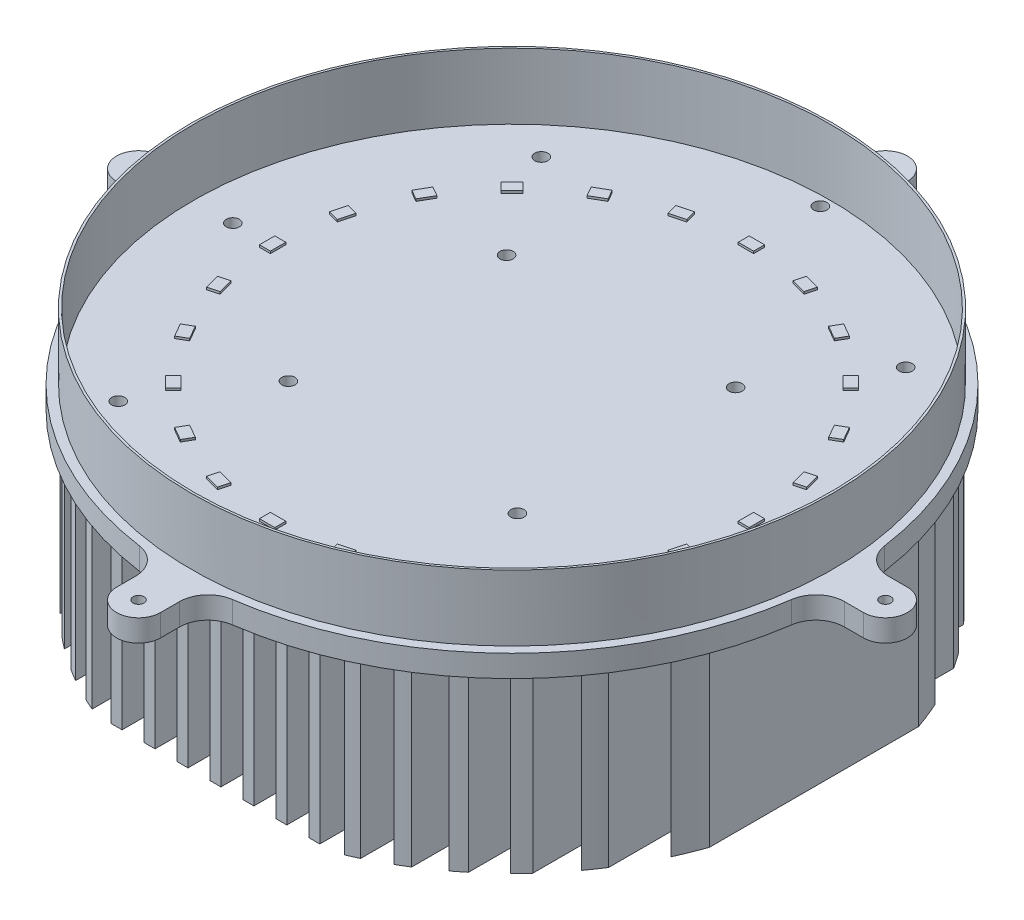
SolidWorks part; units mm, degrees
ref_plane "Front Plane" through (0, 0, 0) normal (0, 0, 1) x (1, 0, 0)
ref_plane "Top Plane" through (0, 0, 0) normal (0, 1, 0) x (1, 0, 0)
ref_plane "Right Plane" through (0, 0, 0) normal (1, 0, 0) x (0, 0, -1)
sketch "Sketch2" plane through (0, 0, 0) normal (0, 1, 0) x (1, 0, 0)
  line L0 (0, 0) -> (0, -224.3017) construction
  line L1 (0, 0) -> (0, 200) construction
  line L2 (0, 0) -> (207.2583, 0) construction
  line L3 (0, 0) -> (-200, 0) construction
  circle A0 centre (0, 0) radius 146
  circle A1 centre (0, 0) radius 145
  point P36 (0, 0)
  dimension "D1" = 290
  dimension "D2" = 292
extrude "Boss-Extrude2" add sketch "Sketch2" along normal blind 30 contours A1 | A0
sketch "Sketch3" plane through (0, 0, 0) normal (0, 1, 0) x (1, 0, 0)
  line L0 (0, 0) -> (211.9111, 0) construction
  line L1 (0, 0) -> (-205.2426, 0) construction
  line L2 (0, 0) -> (0, 170) construction
  line L3 (0, 0) -> (0, -200) construction
  line L4 (161.3691, 10) -> (170, 10)
  line L5 (161.3691, -10) -> (170, -10)
  line L6 (-10, 161.3691) -> (-10, 170)
  line L7 (10, 161.3691) -> (10, 170)
  line L8 (10, -161.3691) -> (10, -170)
  line L9 (-10, -161.3691) -> (-10, -170)
  line L10 (-161.3691, -10) -> (-170, -10)
  line L11 (-161.3691, 10) -> (-170, 10)
  arc A0 (-21.1656, 148.4992) -> (-148.4992, 21.1656) centre (0, 0) ccw
  circle A1 centre (0, 170) radius 2.5
  arc A2 (-10, 170) -> (10, 170) centre (0, 170) cw
  arc A3 (10, 161.3691) -> (21.1656, 148.4992) centre (23, 161.3691) ccw
  arc A4 (-10, 161.3691) -> (-21.1656, 148.4992) centre (-23, 161.3691) cw
  arc A5 (170, 10) -> (170, -10) centre (170, 0) cw
  arc A6 (161.3691, 10) -> (148.4992, 21.1656) centre (161.3691, 23) cw
  circle A7 centre (170, 0) radius 2.5
  arc A8 (161.3691, -10) -> (148.4992, -21.1656) centre (161.3691, -23) ccw
  arc A9 (10, -170) -> (-10, -170) centre (0, -170) cw
  arc A10 (10, -161.3691) -> (21.1656, -148.4992) centre (23, -161.3691) cw
  circle A11 centre (0, -170) radius 2.5
  arc A12 (-10, -161.3691) -> (-21.1656, -148.4992) centre (-23, -161.3691) ccw
  arc A13 (-170, -10) -> (-170, 10) centre (-170, 0) cw
  arc A14 (-161.3691, -10) -> (-148.4992, -21.1656) centre (-161.3691, -23) cw
  circle A15 centre (-170, 0) radius 2.5
  arc A16 (-161.3691, 10) -> (-148.4992, 21.1656) centre (-161.3691, 23) ccw
  arc A17 (-148.4992, -21.1656) -> (-21.1656, -148.4992) centre (0, 0) ccw
  arc A18 (148.4992, 21.1656) -> (21.1656, 148.4992) centre (0, 0) ccw
  arc A19 (21.1656, -148.4992) -> (148.4992, -21.1656) centre (0, 0) ccw
  point P53 (0, 0)
  dimension "D1" = 300
  dimension "D4" = 5
  dimension "D2" = 4
extrude "Boss-Extrude4" add sketch "Sketch3" against normal blind 10
sketch "Sketch4" plane through (0, -10, 0) normal (0, -1, 0) x (1, 0, 0)
  line L0 (0, 0) -> (0, -192.7937) construction
  line L1 (0, 0) -> (0, 216.5128) construction
  line L2 (0, 0) -> (-235.9747, 0) construction
  line L3 (0, 0) -> (242.3846, 0) construction
  line L4 (2.5, -135) -> (-2.5, -135)
  line L5 (2.5, 135) -> (-2.5, 135)
  line L6 (-2.5, -135) -> (-2.5, 135)
  line L7 (2.5, -135) -> (2.5, 135)
  line L8 (12.5, -135) -> (12.5, 135)
  line L9 (17.5, -135) -> (12.5, -135)
  line L10 (17.5, -135) -> (17.5, 135)
  line L11 (17.5, 135) -> (12.5, 135)
  line L12 (27.5, -135) -> (27.5, 135)
  line L13 (32.5, -135) -> (27.5, -135)
  line L14 (32.5, -135) -> (32.5, 135)
  line L15 (32.5, 135) -> (27.5, 135)
  line L16 (42.5, -135) -> (42.5, 135)
  line L17 (47.5, -135) -> (42.5, -135)
  line L18 (47.5, -135) -> (47.5, 135)
  line L19 (47.5, 135) -> (42.5, 135)
  line L20 (57.5, -133.6563) -> (57.5, 133.6563)
  line L22 (62.5, -131.3925) -> (62.5, 131.3925)
  line L24 (72.5, -126.1507) -> (72.5, 126.1507)
  line L26 (77.5, -123.1422) -> (77.5, 123.1422)
  line L28 (87.5, -116.2497) -> (87.5, 116.2497)
  line L30 (92.5, -112.3121) -> (92.5, 112.3121)
  line L32 (102.5, -103.2666) -> (102.5, 103.2666)
  line L34 (107.5, -98.051) -> (107.5, 98.051)
  line L36 (117.5, -85.8138) -> (117.5, 85.8138)
  line L38 (122.5, -78.5111) -> (122.5, 78.5111)
  line L40 (132.5, -60.1166) -> (132.5, 60.1166)
  line L42 (137.5, -47.5815) -> (137.5, 47.5815)
  line L44 (-12.5, -135) -> (-17.5, -135)
  line L45 (-12.5, -135) -> (-12.5, 135)
  line L46 (-17.5, -135) -> (-17.5, 135)
  line L47 (-12.5, 135) -> (-17.5, 135)
  line L48 (-27.5, -135) -> (-32.5, -135)
  line L49 (-27.5, -135) -> (-27.5, 135)
  line L50 (-32.5, -135) -> (-32.5, 135)
  line L51 (-27.5, 135) -> (-32.5, 135)
  line L52 (-42.5, -135) -> (-47.5, -135)
  line L53 (-42.5, -135) -> (-42.5, 135)
  line L54 (-47.5, -135) -> (-47.5, 135)
  line L55 (-42.5, 135) -> (-47.5, 135)
  line L57 (-57.5, -133.6563) -> (-57.5, 133.6563)
  line L58 (-62.5, -131.3925) -> (-62.5, 131.3925)
  line L61 (-72.5, -126.1507) -> (-72.5, 126.1507)
  line L62 (-77.5, -123.1422) -> (-77.5, 123.1422)
  line L65 (-87.5, -116.2497) -> (-87.5, 116.2497)
  line L66 (-92.5, -112.3121) -> (-92.5, 112.3121)
  line L69 (-102.5, -103.2666) -> (-102.5, 103.2666)
  line L70 (-107.5, -98.051) -> (-107.5, 98.051)
  line L73 (-117.5, -85.8138) -> (-117.5, 85.8138)
  line L74 (-122.5, -78.5111) -> (-122.5, 78.5111)
  line L77 (-132.5, -60.1166) -> (-132.5, 60.1166)
  line L78 (-137.5, -47.5815) -> (-137.5, 47.5815)
  line L80 (2.5, -135) -> (-12.5, -135) construction
  line L81 (62.5, 135) -> (57.5, 135) [skipped]
  line L82 (77.5, 135) -> (72.5, 135) [skipped]
  line L83 (92.5, 135) -> (87.5, 135) [skipped]
  line L84 (107.5, 135) -> (102.5, 135) [skipped]
  line L85 (137.5, 135) -> (132.5, 135) [skipped]
  line L86 (122.5, 135) -> (117.5, 135) [skipped]
  line L87 (-57.5, 135) -> (-62.5, 135) [skipped]
  line L88 (-72.5, 135) -> (-77.5, 135) [skipped]
  line L89 (-87.5, 135) -> (-92.5, 135) [skipped]
  line L90 (-102.5, 135) -> (-107.5, 135) [skipped]
  line L91 (-117.5, 135) -> (-122.5, 135) [skipped]
  line L92 (-132.5, 135) -> (-137.5, 135) [skipped]
  line L93 (-57.5, -135) -> (-62.5, -135) [skipped]
  line L94 (62.5, -135) -> (57.5, -135) [skipped]
  line L95 (77.5, -135) -> (72.5, -135) [skipped]
  line L96 (137.5, -135) -> (132.5, -135) [skipped]
  line L97 (122.5, -135) -> (117.5, -135) [skipped]
  line L98 (107.5, -135) -> (102.5, -135) [skipped]
  line L99 (92.5, -135) -> (87.5, -135) [skipped]
  line L100 (-132.5, -135) -> (-137.5, -135) [skipped]
  line L101 (-117.5, -135) -> (-122.5, -135) [skipped]
  line L102 (-102.5, -135) -> (-107.5, -135) [skipped]
  line L103 (-87.5, -135) -> (-92.5, -135) [skipped]
  line L104 (-72.5, -135) -> (-77.5, -135) [skipped]
  arc A2 (132.5, -60.1166) -> (137.5, -47.5815) centre (0, 0) ccw
  arc A3 (117.5, -85.8138) -> (122.5, -78.5111) centre (0, 0) ccw
  arc A4 (102.5, -103.2666) -> (107.5, -98.051) centre (0, 0) ccw
  arc A5 (87.5, -116.2497) -> (92.5, -112.3121) centre (0, 0) ccw
  arc A6 (72.5, -126.1507) -> (77.5, -123.1422) centre (0, 0) ccw
  arc A7 (57.5, -133.6563) -> (62.5, -131.3925) centre (0, 0) ccw
  arc A8 (-77.5, -123.1422) -> (-72.5, -126.1507) centre (0, 0) ccw
  arc A9 (-62.5, -131.3925) -> (-57.5, -133.6563) centre (0, 0) ccw
  arc A10 (-92.5, -112.3121) -> (-87.5, -116.2497) centre (0, 0) ccw
  arc A11 (-107.5, -98.051) -> (-102.5, -103.2666) centre (0, 0) ccw
  arc A12 (-122.5, -78.5111) -> (-117.5, -85.8138) centre (0, 0) ccw
  arc A13 (-137.5, -47.5815) -> (-132.5, -60.1166) centre (0, 0) ccw
  arc A14 (137.5, 47.5815) -> (132.5, 60.1166) centre (0, 0) ccw
  arc A15 (122.5, 78.5111) -> (117.5, 85.8138) centre (0, 0) ccw
  arc A16 (107.5, 98.051) -> (102.5, 103.2666) centre (0, 0) ccw
  arc A17 (92.5, 112.3121) -> (87.5, 116.2497) centre (0, 0) ccw
  arc A18 (77.5, 123.1422) -> (72.5, 126.1507) centre (0, 0) ccw
  arc A19 (62.5, 131.3925) -> (57.5, 133.6563) centre (0, 0) ccw
  arc A20 (-57.5, 133.6563) -> (-62.5, 131.3925) centre (0, 0) ccw
  arc A21 (-72.5, 126.1507) -> (-77.5, 123.1422) centre (0, 0) ccw
  arc A22 (-87.5, 116.2497) -> (-92.5, 112.3121) centre (0, 0) ccw
  arc A23 (-102.5, 103.2666) -> (-107.5, 98.051) centre (0, 0) ccw
  arc A24 (-117.5, 85.8138) -> (-122.5, 78.5111) centre (0, 0) ccw
  arc A25 (-132.5, 60.1166) -> (-137.5, 47.5815) centre (0, 0) ccw
  dimension "D5" = 291
  dimension "D1" = 135
  dimension "D2" = 2.5
  dimension "D4" = 15
  dimension "D3" = 10
extrude "Boss-Extrude5" add sketch "Sketch4" along normal blind 80
sketch "Sketch5" plane through (0, 0, 0) normal (0, 1, 0) x (1, 0, 0)
  line L0 (0, 0) -> (233.0388, 0) construction
  line L1 (0, 0) -> (-266.1331, 0) construction
  line L2 (0, 0) -> (0, 192.8201) construction
  line L3 (0, 0) -> (0, -200.634) construction
  line L4 (0, 111.4786) -> (3.5, 111.4786)
  line L5 (0, 111.4786) -> (-3.5, 111.4786)
  line L6 (3.5, 106.4786) -> (3.5, 111.4786)
  line L7 (-3.5, 106.4786) -> (-3.5, 111.4786)
  line L8 (0, 106.4786) -> (3.5, 106.4786)
  line L9 (0, 106.4786) -> (-3.5, 106.4786)
  line L10 (24.1779, 103.7563) -> (25.472, 108.5859)
  line L11 (28.8528, 107.68) -> (25.472, 108.5859)
  line L12 (28.8528, 107.68) -> (32.2335, 106.7742)
  line L13 (30.9394, 101.9445) -> (32.2335, 106.7742)
  line L14 (27.5587, 102.8504) -> (30.9394, 101.9445)
  line L15 (27.5587, 102.8504) -> (24.1779, 103.7563)
  line L16 (50.2082, 93.9631) -> (52.7082, 98.2933)
  line L17 (55.7393, 96.5433) -> (52.7082, 98.2933)
  line L18 (55.7393, 96.5433) -> (58.7704, 94.7933)
  line L19 (56.2704, 90.4631) -> (58.7704, 94.7933)
  line L20 (53.2393, 92.2131) -> (56.2704, 90.4631)
  line L21 (53.2393, 92.2131) -> (50.2082, 93.9631)
  line L22 (72.8168, 77.7666) -> (76.3524, 81.3021)
  line L23 (78.8273, 78.8273) -> (76.3524, 81.3021)
  line L24 (78.8273, 78.8273) -> (81.3021, 76.3524)
  line L25 (77.7666, 72.8168) -> (81.3021, 76.3524)
  line L26 (75.2917, 75.2917) -> (77.7666, 72.8168)
  line L27 (75.2917, 75.2917) -> (72.8168, 77.7666)
  line L28 (90.4631, 56.2704) -> (94.7933, 58.7704)
  line L29 (96.5433, 55.7393) -> (94.7933, 58.7704)
  line L30 (96.5433, 55.7393) -> (98.2933, 52.7082)
  line L31 (93.9631, 50.2082) -> (98.2933, 52.7082)
  line L32 (92.2131, 53.2393) -> (93.9631, 50.2082)
  line L33 (92.2131, 53.2393) -> (90.4631, 56.2704)
  line L34 (101.9445, 30.9394) -> (106.7742, 32.2335)
  line L35 (107.68, 28.8528) -> (106.7742, 32.2335)
  line L36 (107.68, 28.8528) -> (108.5859, 25.472)
  line L37 (103.7563, 24.1779) -> (108.5859, 25.472)
  line L38 (102.8504, 27.5587) -> (103.7563, 24.1779)
  line L39 (102.8504, 27.5587) -> (101.9445, 30.9394)
  line L40 (106.4786, 3.5) -> (111.4786, 3.5)
  line L41 (111.4786, 0) -> (111.4786, 3.5)
  line L42 (111.4786, 0) -> (111.4786, -3.5)
  line L43 (106.4786, -3.5) -> (111.4786, -3.5)
  line L44 (106.4786, 0) -> (106.4786, -3.5)
  line L45 (106.4786, 0) -> (106.4786, 3.5)
  line L46 (103.7563, -24.1779) -> (108.5859, -25.472)
  line L47 (107.68, -28.8528) -> (108.5859, -25.472)
  line L48 (107.68, -28.8528) -> (106.7742, -32.2335)
  line L49 (101.9445, -30.9394) -> (106.7742, -32.2335)
  line L50 (102.8504, -27.5587) -> (101.9445, -30.9394)
  line L51 (102.8504, -27.5587) -> (103.7563, -24.1779)
  line L52 (93.9631, -50.2082) -> (98.2933, -52.7082)
  line L53 (96.5433, -55.7393) -> (98.2933, -52.7082)
  line L54 (96.5433, -55.7393) -> (94.7933, -58.7704)
  line L55 (90.4631, -56.2704) -> (94.7933, -58.7704)
  line L56 (92.2131, -53.2393) -> (90.4631, -56.2704)
  line L57 (92.2131, -53.2393) -> (93.9631, -50.2082)
  line L58 (77.7666, -72.8168) -> (81.3021, -76.3524)
  line L59 (78.8273, -78.8273) -> (81.3021, -76.3524)
  line L60 (78.8273, -78.8273) -> (76.3524, -81.3021)
  line L61 (72.8168, -77.7666) -> (76.3524, -81.3021)
  line L62 (75.2917, -75.2917) -> (72.8168, -77.7666)
  line L63 (75.2917, -75.2917) -> (77.7666, -72.8168)
  line L64 (56.2704, -90.4631) -> (58.7704, -94.7933)
  line L65 (55.7393, -96.5433) -> (58.7704, -94.7933)
  line L66 (55.7393, -96.5433) -> (52.7082, -98.2933)
  line L67 (50.2082, -93.9631) -> (52.7082, -98.2933)
  line L68 (53.2393, -92.2131) -> (50.2082, -93.9631)
  line L69 (53.2393, -92.2131) -> (56.2704, -90.4631)
  line L70 (30.9394, -101.9445) -> (32.2335, -106.7742)
  line L71 (28.8528, -107.68) -> (32.2335, -106.7742)
  line L72 (28.8528, -107.68) -> (25.472, -108.5859)
  line L73 (24.1779, -103.7563) -> (25.472, -108.5859)
  line L74 (27.5587, -102.8504) -> (24.1779, -103.7563)
  line L75 (27.5587, -102.8504) -> (30.9394, -101.9445)
  line L76 (3.5, -106.4786) -> (3.5, -111.4786)
  line L77 (0, -111.4786) -> (3.5, -111.4786)
  line L78 (0, -111.4786) -> (-3.5, -111.4786)
  line L79 (-3.5, -106.4786) -> (-3.5, -111.4786)
  line L80 (0, -106.4786) -> (-3.5, -106.4786)
  line L81 (0, -106.4786) -> (3.5, -106.4786)
  line L82 (-24.1779, -103.7563) -> (-25.472, -108.5859)
  line L83 (-28.8528, -107.68) -> (-25.472, -108.5859)
  line L84 (-28.8528, -107.68) -> (-32.2335, -106.7742)
  line L85 (-30.9394, -101.9445) -> (-32.2335, -106.7742)
  line L86 (-27.5587, -102.8504) -> (-30.9394, -101.9445)
  line L87 (-27.5587, -102.8504) -> (-24.1779, -103.7563)
  line L88 (-50.2082, -93.9631) -> (-52.7082, -98.2933)
  line L89 (-55.7393, -96.5433) -> (-52.7082, -98.2933)
  line L90 (-55.7393, -96.5433) -> (-58.7704, -94.7933)
  line L91 (-56.2704, -90.4631) -> (-58.7704, -94.7933)
  line L92 (-53.2393, -92.2131) -> (-56.2704, -90.4631)
  line L93 (-53.2393, -92.2131) -> (-50.2082, -93.9631)
  line L94 (-72.8168, -77.7666) -> (-76.3524, -81.3021)
  line L95 (-78.8273, -78.8273) -> (-76.3524, -81.3021)
  line L96 (-78.8273, -78.8273) -> (-81.3021, -76.3524)
  line L97 (-77.7666, -72.8168) -> (-81.3021, -76.3524)
  line L98 (-75.2917, -75.2917) -> (-77.7666, -72.8168)
  line L99 (-75.2917, -75.2917) -> (-72.8168, -77.7666)
  line L100 (-90.4631, -56.2704) -> (-94.7933, -58.7704)
  line L101 (-96.5433, -55.7393) -> (-94.7933, -58.7704)
  line L102 (-96.5433, -55.7393) -> (-98.2933, -52.7082)
  line L103 (-93.9631, -50.2082) -> (-98.2933, -52.7082)
  line L104 (-92.2131, -53.2393) -> (-93.9631, -50.2082)
  line L105 (-92.2131, -53.2393) -> (-90.4631, -56.2704)
  line L106 (-101.9445, -30.9394) -> (-106.7742, -32.2335)
  line L107 (-107.68, -28.8528) -> (-106.7742, -32.2335)
  line L108 (-107.68, -28.8528) -> (-108.5859, -25.472)
  line L109 (-103.7563, -24.1779) -> (-108.5859, -25.472)
  line L110 (-102.8504, -27.5587) -> (-103.7563, -24.1779)
  line L111 (-102.8504, -27.5587) -> (-101.9445, -30.9394)
  line L112 (-106.4786, -3.5) -> (-111.4786, -3.5)
  line L113 (-111.4786, 0) -> (-111.4786, -3.5)
  line L114 (-111.4786, 0) -> (-111.4786, 3.5)
  line L115 (-106.4786, 3.5) -> (-111.4786, 3.5)
  line L116 (-106.4786, 0) -> (-106.4786, 3.5)
  line L117 (-106.4786, 0) -> (-106.4786, -3.5)
  line L118 (-103.7563, 24.1779) -> (-108.5859, 25.472)
  line L119 (-107.68, 28.8528) -> (-108.5859, 25.472)
  line L120 (-107.68, 28.8528) -> (-106.7742, 32.2335)
  line L121 (-101.9445, 30.9394) -> (-106.7742, 32.2335)
  line L122 (-102.8504, 27.5587) -> (-101.9445, 30.9394)
  line L123 (-102.8504, 27.5587) -> (-103.7563, 24.1779)
  line L124 (-93.9631, 50.2082) -> (-98.2933, 52.7082)
  line L125 (-96.5433, 55.7393) -> (-98.2933, 52.7082)
  line L126 (-96.5433, 55.7393) -> (-94.7933, 58.7704)
  line L127 (-90.4631, 56.2704) -> (-94.7933, 58.7704)
  line L128 (-92.2131, 53.2393) -> (-90.4631, 56.2704)
  line L129 (-92.2131, 53.2393) -> (-93.9631, 50.2082)
  line L130 (-77.7666, 72.8168) -> (-81.3021, 76.3524)
  line L131 (-78.8273, 78.8273) -> (-81.3021, 76.3524)
  line L132 (-78.8273, 78.8273) -> (-76.3524, 81.3021)
  line L133 (-72.8168, 77.7666) -> (-76.3524, 81.3021)
  line L134 (-75.2917, 75.2917) -> (-72.8168, 77.7666)
  line L135 (-75.2917, 75.2917) -> (-77.7666, 72.8168)
  line L136 (-56.2704, 90.4631) -> (-58.7704, 94.7933)
  line L137 (-55.7393, 96.5433) -> (-58.7704, 94.7933)
  line L138 (-55.7393, 96.5433) -> (-52.7082, 98.2933)
  line L139 (-50.2082, 93.9631) -> (-52.7082, 98.2933)
  line L140 (-53.2393, 92.2131) -> (-50.2082, 93.9631)
  line L141 (-53.2393, 92.2131) -> (-56.2704, 90.4631)
  line L142 (-30.9394, 101.9445) -> (-32.2335, 106.7742)
  line L143 (-28.8528, 107.68) -> (-32.2335, 106.7742)
  line L144 (-28.8528, 107.68) -> (-25.472, 108.5859)
  line L145 (-24.1779, 103.7563) -> (-25.472, 108.5859)
  line L146 (-27.5587, 102.8504) -> (-24.1779, 103.7563)
  line L147 (-27.5587, 102.8504) -> (-30.9394, 101.9445)
  point P33 (0, 0)
  dimension "D1" = 3.5
  dimension "D2" = 5
  dimension "D3" = 24
extrude "Boss-Extrude6" add sketch "Sketch5" along normal blind 1
sketch "Sketch7" plane through (0, 0, 0) normal (0, 1, 0) x (1, 0, 0)
  line L0 (0, 0) -> (0, 199.2983) construction
  line L1 (180, 0) -> (-209.1437, 0) construction
  line L2 (0, 0) -> (0, -219.846) construction
  arc A0 (170, -10) -> (170, 10) centre (170, 0) ccw construction
  circle A1 centre (-127.0882, 0) radius 3
  circle A2 centre (0, 140.3779) radius 3
  circle A3 centre (0, -140.3779) radius 3
  circle A4 centre (127.0882, 0) radius 3
  circle A6 centre (-52.1309, 49.6625) radius 3
  circle A7 centre (52.1309, 49.6625) radius 3
  circle A8 centre (52.1309, -49.6625) radius 3
  circle A9 centre (-52.1309, -49.6625) radius 3
  circle A11 centre (-82.9543, 96.2809) radius 3
  circle A12 centre (82.9543, 96.2809) radius 3
  circle A13 centre (82.9543, -96.2809) radius 3
  circle A14 centre (-82.9543, -96.2809) radius 3
  dimension "D2" = 6
extrude "Cut-Extrude1" cut sketch "Sketch7" against normal blind 10
